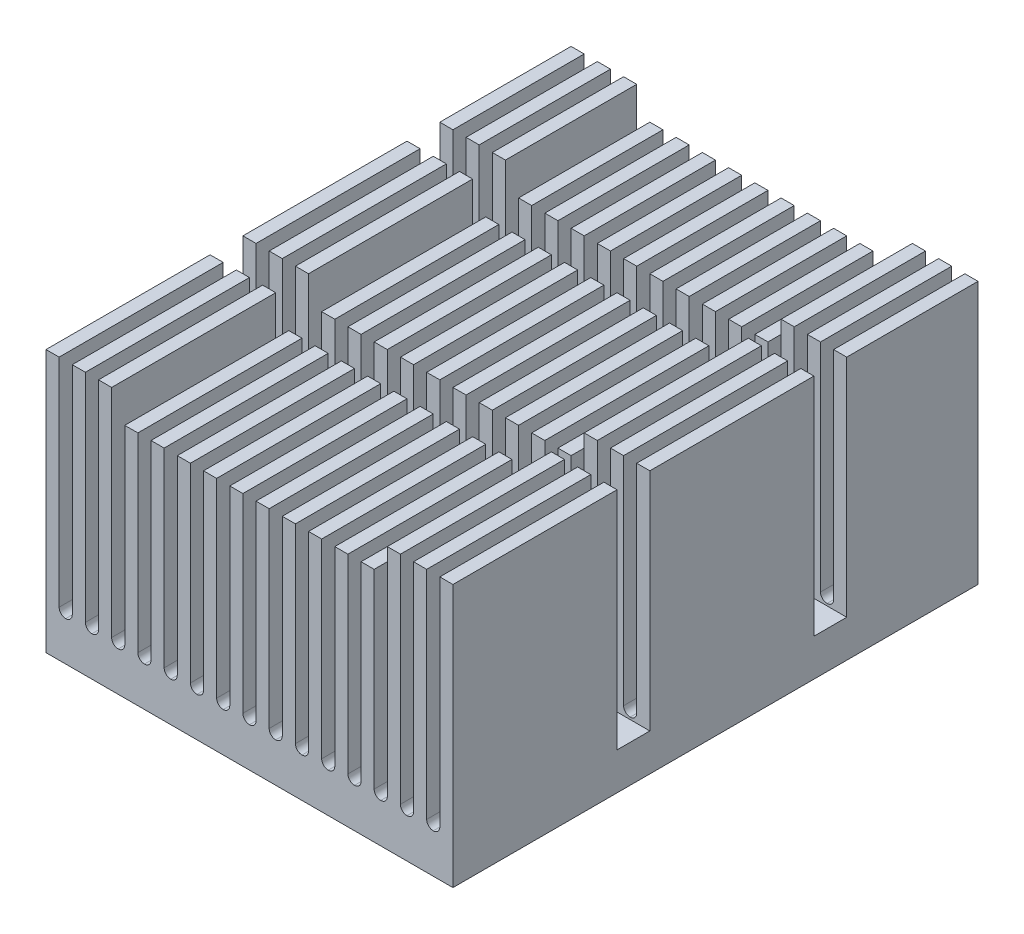
SolidWorks part; units mm, degrees
ref_plane "Front Plane" through (0, 0, 0) normal (0, 0, 1) x (1, 0, 0)
ref_plane "Top Plane" through (0, 0, 0) normal (0, 1, 0) x (1, 0, 0)
ref_plane "Right Plane" through (0, 0, 0) normal (1, 0, 0) x (0, 0, -1)
sketch "Sketch1" plane through (0, 0, 0) normal (0, 0, 1) x (1, 0, 0)
  line L0 (0, 44.1341) -> (0, 0) construction
  line L2 (31, 2.067) -> (-31, 2.067)
  line L3 (31, 2.067) -> (31, 42.067)
  line L4 (31, 42.067) -> (-31, 42.067)
  line L5 (-31, 2.067) -> (-31, 42.067)
  line L6 (31, 2.067) -> (-31, 42.067) construction
  line L7 (31, 42.067) -> (-31, 2.067) construction
  point P3 (0, 22.067)
  dimension "D1" = 40
  dimension "D2" = 62
extrude "Boss-Extrude1" add sketch "Sketch1" along normal mid plane 80
sketch "Sketch2" plane through (0, 0, 0) normal (0, 0, 1) x (1, 0, 0)
  line L0 (31, 42.067) -> (-31, 42.067) construction
  line L1 (-29, 42.067) -> (-27, 42.067)
  line L2 (-29, 42.067) -> (-29, 8.067)
  line L3 (-29, 8.067) -> (-27, 8.067)
  line L4 (-27, 42.067) -> (-27, 8.067)
  line L5 (-31, 42.067) -> (-31, 2.067) construction
  dimension "D1" = 2
  dimension "D2" = 2
  dimension "D3" = 34
extrude "Cut-Extrude1" cut sketch "Sketch2" against normal mid plane 80
fillet "Fillet1" radius 1 2 edges at (-29, 8.067, 0) (-27, 8.067, 0)
pattern_linear "LPattern2" count 15 spacing 4 along (1, 0, 0) of "Cut-Extrude1", "Fillet1"
sketch "Sketch4" plane through (0, 0, 0) normal (0, 0, 1) x (1, 0, 0)
  line L0 (0, 0) -> (0, 47.2372) construction
  line L2 (-20, 42.067) -> (20, 42.067)
  line L3 (-20, 42.067) -> (-20, 38.067)
  line L4 (-20, 38.067) -> (20, 38.067)
  line L5 (20, 42.067) -> (20, 38.067)
  dimension "D1" = 40
  dimension "D2" = 4
extrude "Cut-Extrude2" cut sketch "Sketch4" against normal mid plane 80
sketch "Sketch5" plane through (0, 0, 0) normal (1, 0, 0) x (0, 0, -1)
  line L0 (-40, 42.067) -> (40, 42.067) construction
  line L1 (-15, 42.067) -> (-10, 42.067)
  line L2 (-15, 42.067) -> (-15, 7.7387)
  line L3 (-15, 7.7387) -> (-10, 7.7387)
  line L4 (-10, 42.067) -> (-10, 7.7387)
  line L5 (-40, 2.067) -> (-40, 42.067) construction
  line L6 (20, 42.067) -> (15, 42.067)
  line L7 (20, 42.067) -> (20, 7.7387)
  line L8 (20, 7.7387) -> (15, 7.7387)
  line L9 (15, 42.067) -> (15, 7.7387)
  line L10 (40, 2.067) -> (40, 42.067) construction
  dimension "D1" = 25
  dimension "D2" = 25
  dimension "D3" = 5
  dimension "D4" = 5
extrude "Cut-Extrude3" cut sketch "Sketch5" against normal mid plane 80
sketch "Sketch6" plane through (0, 2.067, 0) normal (0, -1, 0) x (1, 0, 0)
  line L1 (-6, -6) -> (6, -6)
  line L2 (-6, -6) -> (-6, 6)
  line L3 (-6, 6) -> (6, 6)
  line L4 (6, -6) -> (6, 6)
  line L5 (-6, -6) -> (6, 6) construction
  line L6 (-6, 6) -> (6, -6) construction
  point P0 (0, 0)
  dimension "D1" = 12
  dimension "D2" = 12
split line "Split Line1"
